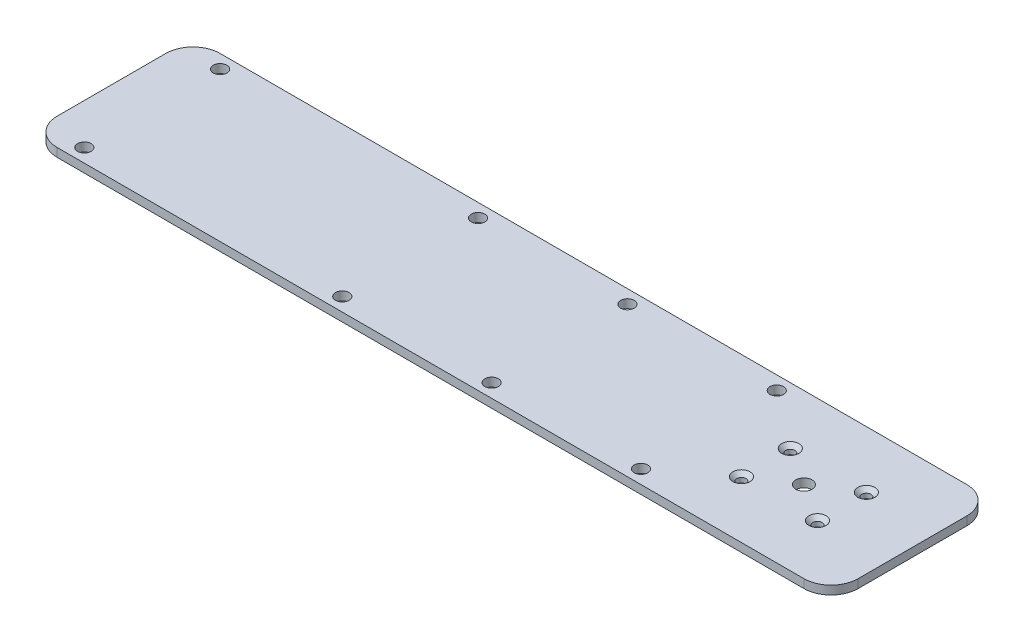
SolidWorks part; units mm, degrees
ref_plane "Front Plane" through (0, 0, 0) normal (0, 0, 1) x (1, 0, 0)
ref_plane "Top Plane" through (0, 0, 0) normal (0, 1, 0) x (1, 0, 0)
ref_plane "Right Plane" through (0, 0, 0) normal (1, 0, 0) x (0, 0, -1)
sketch "Sketch1" plane through (0, 0, 0) normal (0, 1, 0) x (1, 0, 0)
  line L0 (-55, 0) -> (0, 0) construction
  line L1 (-55, 30) -> (240, 30)
  line L2 (-55, 30) -> (-55, -30)
  line L3 (-55, -30) -> (240, -30)
  line L4 (240, 30) -> (240, -30)
  point P7 (200, 0)
  dimension "D1" = 60
  dimension "D2" = 55
  dimension "D3" = 200
  dimension "D4" = 40
extrude "Boss-Extrude1" add sketch "Sketch1" along normal blind 3.175
fillet "Fillet1" radius 10 4 edges at (-55, 1.5875, 30) (-55, 1.5875, -30) (240, 1.5875, 30) (240, 1.5875, -30)
hole_wizard "Ø6.0mm Dowel Hole1" positions "Sketch2" profile "Sketch3" hole size "Ø6.0" standard "DIN" end condition up to next
sketch "Sketch2" plane through (0, 3.175, 0) normal (0, 1, 0) x (1, 0, 0)
  point P0 (200, 0)
  dimension "D1" = 200
sketch "Sketch3" plane through (200, 3.175, 0) normal (1, 0, 0) x (0, 0, 1)
  line L0 (0, 0) -> (0, 3.175)
  line L1 (0, 3.175) -> (3, 3.175)
  line L2 (3, 3.175) -> (3, 0)
  line L5 (3, 0) -> (0, 0)
  line L11 (0, -6.35) -> (0, 107.95) construction
  dimension "Thru Hole Dia." = 6
  dimension "Thru Hole Depth" = 3.175
hole_wizard "CSK for M3 Flat Head Machine Screw1" positions "Sketch4" profile "Sketch5" countersink size "M3" standard "ANSI Metric" end condition up to next
sketch "Sketch4" plane through (0, 3.175, 0) normal (0, 1, 0) x (1, 0, 0)
  line L0 (214, -9) -> (186, -9) construction
  line L1 (214, -9) -> (214, 9) construction
  circle A0 centre (200, 0) radius 3 construction
  point P0 (214, -9)
  point P7 (186, -9)
  point P8 (186, 9)
  point P9 (214, 9)
  dimension "D3" = 28
  dimension "D4" = 18
  dimension "D5" = 14
  dimension "D6" = 9
  dimension "D1" = 2
  dimension "D2" = 2
sketch "Sketch5" plane through (214, 3.175, 9) normal (1, 0, 0) x (0, 0, 1)
  line L0 (0, 0) -> (0, 3.175)
  line L1 (0, 3.175) -> (1.7, 3.175)
  line L2 (1.7, 3.175) -> (1.7, 1.45)
  line L3 (1.7, 1.45) -> (3.15, 0)
  line L5 (3.15, 0) -> (0, 0)
  line L6 (-1.7, 1.45) -> (-3.15, 0) construction
  line L11 (0, -6.35) -> (0, 107.95) construction
  dimension "Thru Hole Dia." = 3.4
  dimension "Thru Hole Depth" = 3.175
  dimension "Near C'Sink Dia." = 6.3
  dimension "Near C'Sink Angle" = 90
hole_wizard "Ø5.0mm Dowel Hole1" positions "Sketch6" profile "Sketch7" hole size "Ø5.0" standard "DIN" end condition through all
sketch "Sketch6" plane through (0, 3.175, 0) normal (0, 1, 0) x (1, 0, 0)
  line L0 (-45, -30) -> (230, -30) construction
  line L1 (55, -25) -> (110, -25) construction
  line L2 (-55, 0) -> (240, 0) construction
  line L3 (-55, 20) -> (-55, -20) construction
  line L4 (240, -20) -> (240, 20) construction
  point P0 (55, -25)
  point P10 (110, -25)
  point P11 (165, -25)
  point P23 (165, 25)
  point P24 (110, 25)
  point P25 (55, 25)
  point P26 (-40, -25)
  point P29 (-40, 25)
  dimension "D1" = 5
  dimension "D2" = 55
  dimension "D4" = 55
  dimension "D5" = 15
  dimension "D3" = 3
sketch "Sketch7" plane through (55, 3.175, 25) normal (1, 0, 0) x (0, 0, 1)
  line L0 (0, 0) -> (0, 3.175)
  line L1 (0, 3.175) -> (2.5, 3.175)
  line L2 (2.5, 3.175) -> (2.5, 0)
  line L5 (2.5, 0) -> (0, 0)
  line L11 (0, -6.35) -> (0, 107.95) construction
  dimension "Thru Hole Dia." = 5
  dimension "Thru Hole Depth" = 3.175
equation "\"Pivot to Pivot Dist\"= 200"
equation "\"D3@Sketch1\"=\"Pivot to Pivot Dist\""
equation "\"D1@Sketch2\"=\"Pivot to Pivot Dist\""
